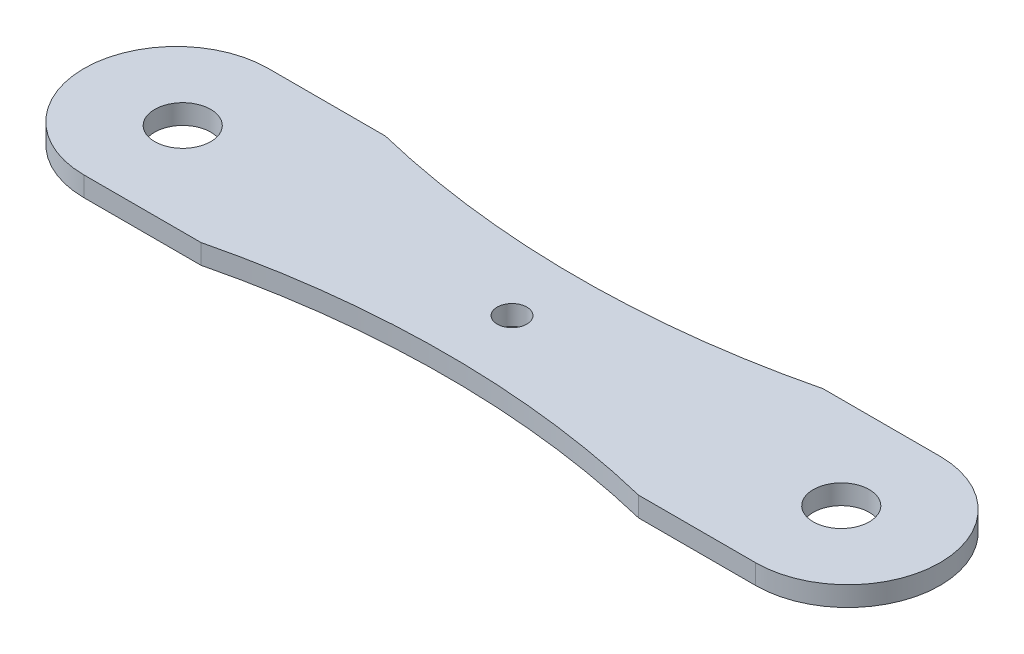
SolidWorks part; units mm, degrees
ref_plane "前视" through (0, 0, 0) normal (0, 0, 1) x (1, 0, 0)
ref_plane "上视" through (0, 0, 0) normal (0, 1, 0) x (1, 0, 0)
ref_plane "右视" through (0, 0, 0) normal (1, 0, 0) x (0, 0, -1)
sketch "草图1" plane through (0, 0, 0) normal (0, 1, 0) x (1, 0, 0)
  line L1 (-65, 14) -> (65, 14)
  line L2 (-65, 14) -> (-65, -14)
  line L3 (-65, -14) -> (65, -14)
  line L4 (65, 14) -> (65, -14)
  line L5 (-65, 14) -> (65, -14) construction
  line L6 (-65, -14) -> (65, 14) construction
  point P0 (0, 0)
  dimension "D1" = 130
  dimension "D2" = 28
extrude "凸台-拉伸1" add sketch "草图1" along normal blind 3 contours L2 | L2 | L3 L1 | L4 | L4 region at (0, 0, 0)
sketch "草图2" plane through (0, 3, 0) normal (0, 1, 0) x (1, 0, 0)
  circle A0 centre (-50, 0) radius 4.25
  circle A1 centre (50, 0) radius 4.25
  circle A2 centre (0, 0) radius 2.25
  dimension "D1" = 8.5
  dimension "D2" = 8.5
  dimension "D5" = 4.5
  dimension "D3" = 100
  dimension "D4" = 50
extrude "切除-拉伸1" cut sketch "草图2" against normal up to next
fillet "圆角1" 2 edges at (-65, 1.5, 14) (-65, 1.5, -14) type full round first side face at (0, 1.5, 14) second side face at (0, 1.5, -14) middle face at (-65, 1.5, 0)
sketch "草图3" plane through (0, 3, 0) normal (0, 1, 0) x (1, 0, 0)
  circle A0 centre (-68.5, 0) radius 2.25
  circle A1 centre (-31.5, 0) radius 2.25
  circle A2 centre (31.5, 0) radius 2.25
  circle A3 centre (68.5, 0) radius 2.25
  circle A4 centre (-50, 0) radius 4.25 construction
  circle A5 centre (50, 0) radius 4.25 construction
  dimension "D2" = 18.5
  dimension "D3" = 4.5
  dimension "D4" = 4.5
  dimension "D6" = 18.5
  dimension "D7" = 4.5
  dimension "D8" = 4.5
  dimension "D1" = 37
  dimension "D5" = 37
extrude "切除-拉伸2" [suppressed] cut sketch "草图3" against normal up to next
sketch "草图4" plane through (0, 3, 0) normal (0, 1, 0) x (1, 0, 0)
  circle A0 centre (0, 150) radius 140
  dimension "D2" = 280
  dimension "D1" = 150
extrude "切除-拉伸3" cut sketch "草图4" against normal up to next
mirror "镜向1" about plane through (0, 0, 0) normal (0, 0, 1) of "切除-拉伸3"
fillet "圆角2" 2 edges at (65, 1.5, 14) (65, 1.5, -14) type full round first side face at (49.1132, 1.5, 14) second side face at (49.1132, 1.5, -14) middle face at (65, 1.5, 0)
